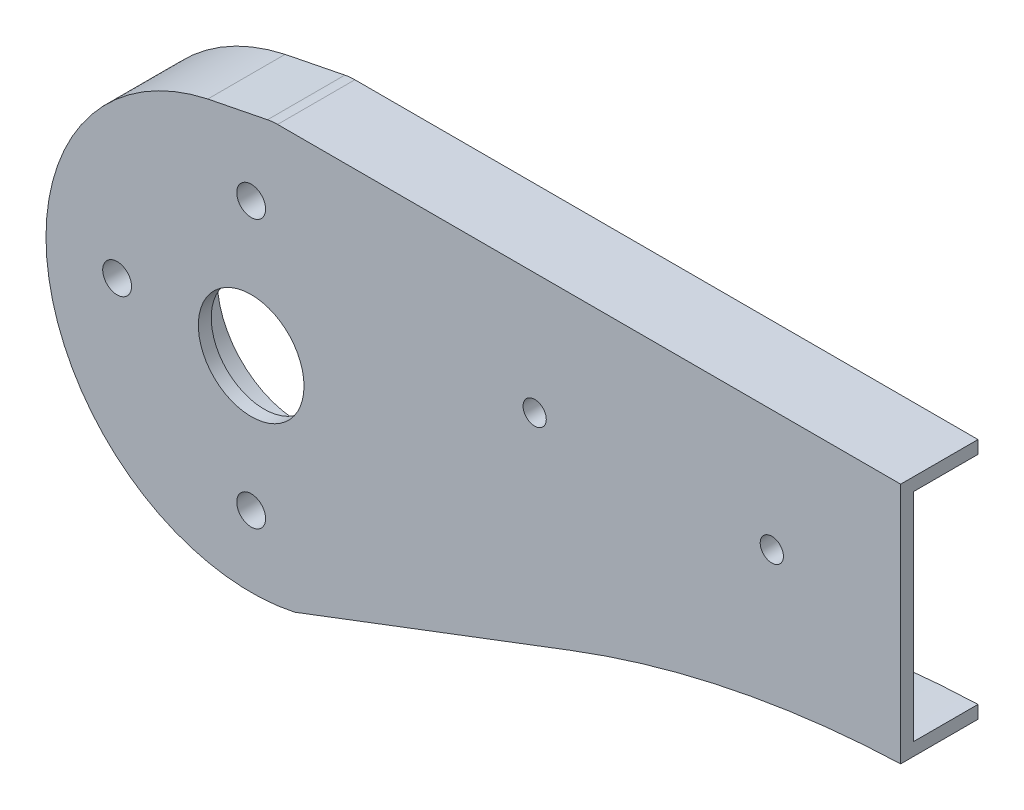
SolidWorks part; units mm, degrees
material "ABS"
ref_plane "Piano frontale" through (0, 0, 0) normal (0, 0, 1) x (1, 0, 0)
ref_plane "Piano superiore" through (0, 0, 0) normal (0, 1, 0) x (1, 0, 0)
ref_plane "Piano destro" through (0, 0, 0) normal (1, 0, 0) x (0, 0, -1)
sketch "Schizzo1" plane through (0, 0, 0) normal (0, 0, 1) x (1, 0, 0)
  line L0 (5.1235, 41.4) -> (126, 41.4)
  line L1 (126, 41.4) -> (126, -5.6)
  line L2 (126, -5.6) -> (96, -5.6) construction
  line L3 (55, 17.9) -> (101, 17.9) construction
  line L4 (3.1704, 41.2074) -> (-8.4161, 38.9)
  line L5 (-8.4161, 38.9) -> (8.4161, -38.9) construction
  line L6 (8.4161, -38.9) -> (96, -5.6) construction
  line L7 (133.0662, -205.4751) -> (61.1004, -16.1945) construction
  line L8 (8.4161, -38.9) -> (61.9889, -18.5312)
  line L9 (7.8874, -36.4565) -> (61.1004, -16.1945)
  line L10 (-7.8874, 36.4565) -> (3.4151, 38.7074)
  line L11 (5.3683, 38.9) -> (126, 38.9)
  arc A0 (-7.1287, 39.1564) -> (8.4161, -38.9) centre (0, 0) ccw
  circle A1 centre (55, 17.9) radius 7.6836 construction
  circle A2 centre (101, 17.9) radius 7.6836 construction
  arc A3 (126, -5.6) -> (61.9889, -18.5312) centre (133.0662, -205.4751) ccw
  arc A4 (126, -3.0985) -> (61.1004, -16.1945) centre (133.0662, -205.4751) ccw
  arc A5 (-7.8874, 36.4565) -> (7.8874, -36.4565) centre (0, 0) ccw
  arc A6 (5.3683, 38.9) -> (3.4151, 38.7074) centre (5.3683, 28.9) ccw
  arc A7 (5.1235, 41.4) -> (3.1704, 41.2074) centre (5.1235, 31.4) ccw
  point P26 (4.1374, 41.4)
  dimension "D1" = 79.6
  dimension "D11" = 400
  dimension "D12" = 2.5
  dimension "D13" = 2.5
  dimension "D15" = 10
  dimension "D2" = 55
  dimension "D3" = 17.9
  dimension "D4" = 23.5
  dimension "D5" = 30
  dimension "D6" = 47
  dimension "D7" = 25
  dimension "D8" = 12.8
  dimension "D9" = 2.5
  dimension "D10" = 46
  dimension "D14" = 2.5
extrude "Estrusione-Estrusione1" add sketch "Schizzo1" against normal blind 2.5 contours L11 A6 L10 A5 L9 A4 L1 | L0 A7 L4 A0 L8 A3 L1 A4 L9 A5 L10 A6 L11 region at (65.5617, 39.5538, 0) region at (38.9445, 7.3362, 0)
extrude "Estrusione-Estrusione2" add sketch "Schizzo1<3>" against normal blind 15 contours L0 A7 L4 A0 L8 A3 L1 A4 L9 A5 L10 A6 L11 region at (65.5617, 39.5538, 0)
sketch "Schizzo1<3>" plane through (0, 0, 0) normal (0, 0, 1) x (1, 0, 0) same geometry as "Schizzo1"
sketch "Schizzo2" plane through (0, 0, 0) normal (0, 0, 1) x (1, 0, 0)
  circle A0 centre (0, 0) radius 10.25
  circle A1 centre (0, 0) radius 26 construction
  circle A2 centre (0, -26) radius 2.8
  circle A3 centre (26, 0) radius 2.8 construction
  circle A4 centre (0, 26) radius 2.8
  circle A5 centre (-26, 0) radius 2.8
  dimension "D1" = 20.5
  dimension "D2" = 52
  dimension "D3" = 5.6
extrude "Taglio-Estrusione1" cut sketch "Schizzo2" against normal blind 15
sketch "Schizzo3" plane through (0, 0, -2.5) normal (0, 0, -1) x (-1, 0, 0)
  line L0 (-101, 17.9) -> (-55, 17.9) construction
  line L1 (-126, 38.9) -> (-126, -3.0985) construction
  line L2 (-26, 0) -> (0, 0) construction
  circle A0 centre (0, 0) radius 14.5
  circle A1 centre (0, 0) radius 16.1
  circle A2 centre (0, 0) radius 18.6
  circle A3 centre (0, 26) radius 2.8
  circle A4 centre (26, 0) radius 2.8
  circle A5 centre (0, -26) radius 2.8
  circle A6 centre (-26, 0) radius 2.8
  circle A7 centre (-26, 0) radius 5
  circle A8 centre (0, -26) radius 5
  circle A9 centre (26, 0) radius 5
  circle A10 centre (0, 26) radius 5
  circle A11 centre (-101, 17.9) radius 6.3
  circle A12 centre (-55, 17.9) radius 6.3
  circle A13 centre (-101, 17.9) radius 2.25
  circle A14 centre (-55, 17.9) radius 2.25
  circle M8 centre (0, -26) radius 2.8
  circle M10 centre (0, 26) radius 2.8
  circle M11 centre (26, 0) radius 2.8
  dimension "D1" = 29
  dimension "D2" = 32.2
  dimension "D3" = 37.2
  dimension "D4" = 5.6
  dimension "D5" = 10
  dimension "D9" = 12.6
  dimension "D10" = 4.5
  dimension "D6" = 17.9
  dimension "D7" = 25
  dimension "D8" = 55
  dimension "D11" = 26
extrude "Estrusione-Estrusione3" add sketch "Schizzo3" along normal blind 0.5 contours A1 A0 region at (15.6446, 0, -2.5)
extrude "Estrusione-Estrusione4" add sketch "Schizzo3<3>" along normal blind 3 contours A12 A14 | A13 A11 region at (107.1218, 17.9, -2.5) region at (61.1218, 17.9, -2.5)
sketch "Schizzo3<3>" plane through (0, 0, -2.5) normal (0, 0, -1) x (-1, 0, 0) same geometry as "Schizzo3"
extrude "Estrusione-Estrusione5" add sketch "Schizzo3<4>" along normal blind 5.6 contours A10 M10 | A9 M11 | A7 | A8 M8 region at (30.8586, 0, -2.5) region at (4.8586, -26, -2.5) region at (-21.1414, 0, -2.5) region at (4.8586, 26, -2.5)
sketch "Schizzo3<4>" plane through (0, 0, -2.5) normal (0, 0, -1) x (-1, 0, 0) same geometry as "Schizzo3"
extrude "Estrusione-Estrusione6" add sketch "Schizzo3<5>" along normal blind 7 contours A2 A1 region at (18.0739, 0, -2.5)
sketch "Schizzo3<5>" plane through (0, 0, -2.5) normal (0, 0, -1) x (-1, 0, 0) same geometry as "Schizzo3"
chamfer "Smusso1" distance 1.5 angle 45 7 edges at (94.7, 17.9, -5.5) (48.7, 17.9, -5.5) (-21, 0, -2.5) (5, 26, -2.5) (5, -26, -2.5) (31, 0, -2.5) (18.6, 0, -2.5)
sketch "Schizzo4" plane through (0, 0, 0) normal (0, 0, 1) x (1, 0, 0)
  line L0 (55, 17.9) -> (101, 17.9) construction
  line L2 (126, 41.4) -> (126, -5.6) construction
  point P0 (55, 17.9)
  point P2 (101, 17.9)
  dimension "D1" = 25
  dimension "D2" = 55
  dimension "D3" = 17.9
hole_wizard "Foro per Vite M4-1" positions "Schizzo4" profile "Schizzo5" hole size "M4" standard "ISO"
sketch "Schizzo5" plane through (55, 17.9, 0) normal (1, 0, 0) x (0, -1, 0)
  line L0 (0, 0) -> (0, 51.3519)
  line L1 (0, 51.3519) -> (2.25, 50)
  line L2 (2.25, 50) -> (2.25, 0)
  line L5 (2.25, 0) -> (0, 0)
  line L10 (0, 51.3519) -> (-2.25, 50) construction
  line L11 (0, -6.35) -> (0, 107.95) construction
  dimension "Hole Dia." = 4.5
  dimension "Hole Depth" = 50
  dimension "Drill Angle" = 118
